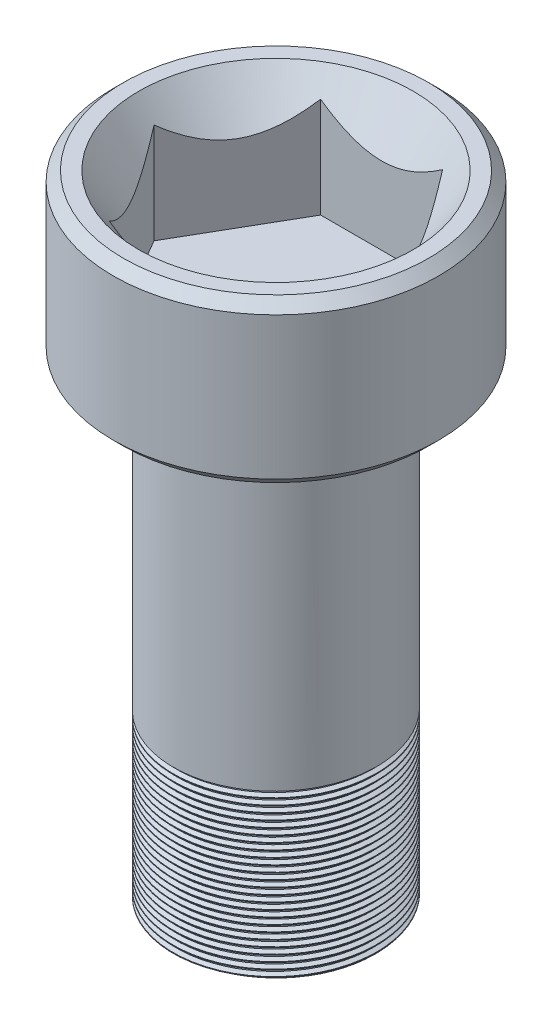
SolidWorks part; units mm, degrees
ref_plane "Front Plane" through (0, 0, 0) normal (0, 0, 1) x (1, 0, 0)
ref_plane "Top Plane" through (0, 0, 0) normal (0, 1, 0) x (1, 0, 0)
ref_plane "Right Plane" through (0, 0, 0) normal (1, 0, 0) x (0, 0, -1)
sketch "Sketch1" plane through (0, 0, 0) normal (0, 1, 0) x (1, 0, 0)
  circle A0 centre (0, 0) radius 8
  dimension "D1" = 16
extrude "Boss-Extrude1" add sketch "Sketch1" against normal blind 11
sketch "Sketch2" plane through (0, -11, 0) normal (0, -1, 0) x (1, 0, 0)
  circle A0 centre (0, 0) radius 5
  dimension "D1" = 10
extrude "Boss-Extrude2" add sketch "Sketch2" along normal blind 25
sketch "Sketch3" plane through (0, 0, 0) normal (0, 1, 0) x (1, 0, 0)
  line L1 (6, 0) -> (3, 5.1962)
  line L2 (3, 5.1962) -> (-3, 5.1962)
  line L3 (-3, 5.1962) -> (-6, 0)
  line L4 (-6, 0) -> (-3, -5.1962)
  line L5 (-3, -5.1962) -> (3, -5.1962)
  line L6 (3, -5.1962) -> (6, 0)
  circle A0 centre (0, 0) radius 5.1962 construction
  dimension "D1" = 6
extrude "Cut-Extrude1" cut sketch "Sketch3" against normal blind 9
chamfer "Chamfer1" distance 0.5 angle 45 1 edges at (0, 0, 8)
chamfer "Chamfer2" distance 0.5 angle 45 1 edges at (0, -11, 8)
thread "Thread2" pitch 0.3175 method cut profile "Thread Profile6" start angle 0, offset 0, length 0, pitch 0.3175, diameter 10
ref_plane "Plane7" through (5, -36, 0) normal (0, 0, 1) x (1, 0, 0)
sketch "Thread Profile6" plane through (5, -36, 0) normal (0, 0, 1) x (1, 0, 0)
  line L0 (0, 0) -> (0, 0.3175) construction
  line L11 (0, 0) -> (0, 0.2778)
  line L12 (0, 0.2778) -> (-0.1719, 0.1786)
  line L13 (-0.1719, 0.1786) -> (-0.1719, 0.0992)
  line L15 (-0.1719, 0.0992) -> (0, 0)
  line L17 (-0.1719, 0.1389) -> (0, 0.1389) construction
  point P2 (0, 0)
  dimension "Pitch" = 0.3175
  dimension "Profile_Angle" = 60
  dimension "Profile_Land" = 0.0794
  dimension "Profile_Height" = 0.1719
sketch "Sketch59" plane through (0, -36, 0) normal (0, -1, 0) x (1, 0, 0)
  circle A0 centre (0, 0) radius 7.5
  dimension "D1" = 15
extrude "Cut-Extrude2" cut sketch "Sketch59" against normal blind 2
sketch "Sketch60" plane through (0, 0, 0) normal (0, 1, 0) x (1, 0, 0)
  circle A0 centre (0, 0) radius 15
  dimension "D1" = 30
extrude "Cut-Extrude3" cut sketch "Sketch60" against normal blind 3
chamfer "Chamfer5" distance 0.5 angle 45 1 edges at (0, -3, 8)
sketch "Sketch61" plane through (0, 0, 0) normal (0, 0, 1) x (1, 0, 0)
  line L0 (0, 0) -> (0, 50000) construction
  line L1 (-6.9576, -2.7152) -> (-4.2052, -6.591)
  line L2 (-4.2052, -6.591) -> (-4.2052, -2.7152)
  line L3 (-4.2052, -2.7152) -> (-6.9576, -2.7152)
revolve "Cut-Revolve1" cut sketch "Sketch61" angle 360 about L0
